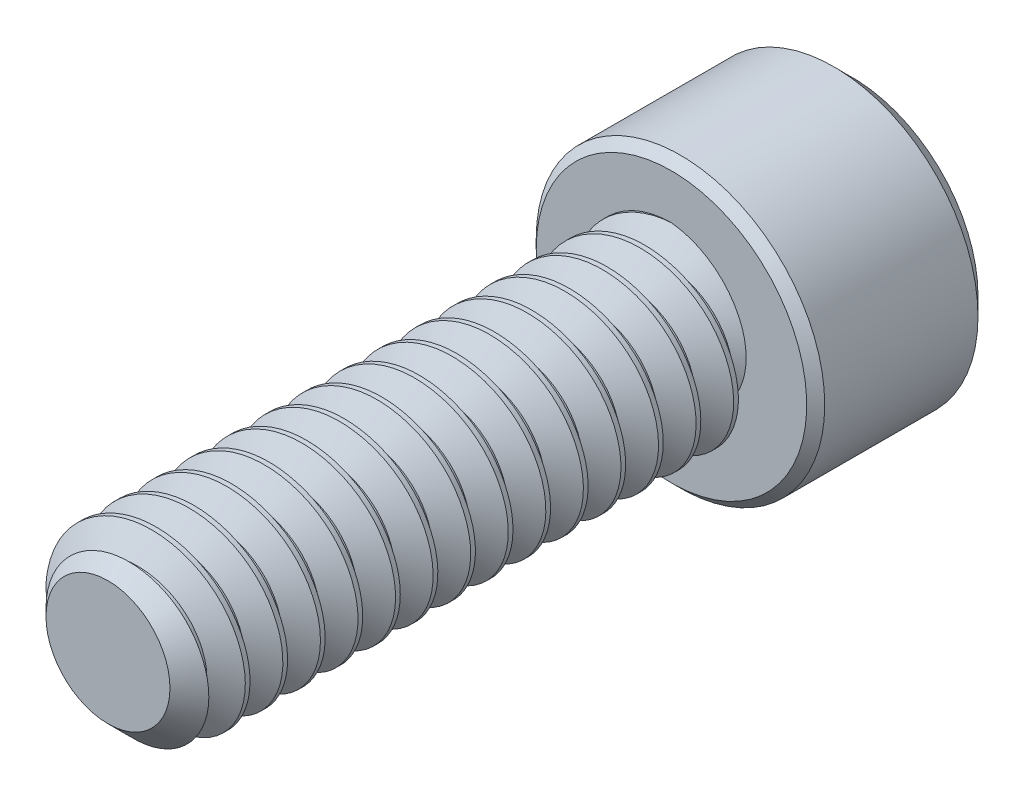
SolidWorks part; units mm, degrees
ref_plane "Front Plane" through (0, 0, 0) normal (0, 0, 1) x (1, 0, 0)
ref_plane "Top Plane" through (0, 0, 0) normal (0, 1, 0) x (1, 0, 0)
ref_plane "Right Plane" through (0, 0, 0) normal (1, 0, 0) x (0, 0, -1)
sketch "Sketch1" plane through (0, 0, 0) normal (0, 0, 1) x (1, 0, 0)
  line L0 (0, 0.762) -> (0, -0.762) construction
  circle A0 centre (0, 0) radius 0.762
  dimension "OD" = 1.524
extrude "Extrude1" add sketch "Sketch1" against normal blind 4.7625
sketch "Sketch2" plane through (0, 0, 0) normal (0, 0, 1) x (1, 0, 0)
  circle A0 centre (0, 0) radius 0.762 construction
  circle A1 centre (0, 0) radius 0.762
curve "Helix/Spiral1" pitch 0.3175 height 5.08 radius 0.762 centre (0, 0, 0) axis (0, 0, -1) start towards (0, 1, 0) parameters "pitch"=0.3175
chamfer "Chamfer3" distance 0.2381 angle 45 1 edges at (0.762, 0, 0)
sketch "Sketch3" plane through (0, 0, 0) normal (1, 0, 0) x (0, 0, -1)
  line L0 (-0.2778, 0.762) -> (-0.1588, 0.5558)
  line L1 (-0.1588, 0.5558) -> (-0.1191, 0.5558)
  line L2 (-0.1191, 0.5558) -> (0, 0.762)
  line L3 (-0.2778, 0.762) -> (0, 0.762)
  line L4 (-0.1389, 0.762) -> (-0.1389, 0.5558) construction
  line L5 (-0.2183, 0.6589) -> (-0.0595, 0.6589) construction
  line L6 (0, 0.762) -> (0, -0.762) construction
  dimension "D1" = 0.0397
  dimension "D2" = 0.1588
  dimension "D3" = 60
sweep "Cut-Sweep1" cut profiles "Sketch3" path "Helix/Spiral1" align with end faces yes
sketch "Sketch6" plane through (0, 0, -4.7625) normal (0, 0, -1) x (-1, 0, 0)
  circle A0 centre (0, 0) radius 1.2192
  dimension "head dia" = 2.4384
extrude "Extrude2" add sketch "Sketch6" along normal blind 1.524
sketch "Sketch7" plane through (0, 0, -6.2865) normal (0, 0, -1) x (-1, 0, 0)
  line L1 (0, 0.7332) -> (-0.635, 0.3666)
  line L2 (-0.635, 0.3666) -> (-0.635, -0.3666)
  line L3 (-0.635, -0.3666) -> (0, -0.7332)
  line L4 (0, -0.7332) -> (0.635, -0.3666)
  line L5 (0.635, -0.3666) -> (0.635, 0.3666)
  line L6 (0.635, 0.3666) -> (0, 0.7332)
  circle A0 centre (0, 0) radius 0.635 construction
  dimension "hex dia" = 1.27
extrude "Cut-Extrude1" cut sketch "Sketch7" against normal blind 0.9525
sketch "Sketch8" plane through (0, 0, -6.2865) normal (0, 0, -1) x (-1, 0, 0)
  circle A0 centre (0, 0) radius 0.7332
extrude "Cut-Extrude2" cut sketch "Sketch8" against normal blind 0.1524 draft 45
chamfer "Chamfer1" distance 0.1524 angle 45 1 edges at (-1.2192, 0, -6.2865)
chamfer "Chamfer2" distance 0.0762 angle 45 1 edges at (-1.2192, 0, -4.7625)
sketch "Sketch9" plane through (0, 0, 0) normal (1, 0, 0) x (0, 0, -1)
  line L0 (0, 0.762) -> (0, -0.762) construction
  line L1 (1.7463, 0.762) -> (1.7463, -0.762) construction
  line L2 (4.7625, 1.2192) -> (4.7625, -1.2192) construction
  line L3 (6.2865, 1.2192) -> (6.2865, -1.2192) construction
  line L4 (6.2865, 0) -> (0, 0) construction
  dimension "D1" = 1.7463
  dimension "D2" = 1.524
  dimension "D3" = 2.4384
  dimension "D4" = 4.7625
equation "\"D3@Helix/Spiral1\" = \"screw length@Extrude1\"+\"pitch@Helix/Spiral1\""
equation "\"D1@Sketch3\" = \"pitch@Helix/Spiral1\"*.125"
equation "\"D2@Sketch3\" = \"pitch@Helix/Spiral1\"*.5"
equation "\"D1@Cut-Extrude1\" = \"hex dia@Sketch7\"*.75"
equation "\"D1@Chamfer1\" = \"head depth@Extrude2\"/10"
equation "\"D1@Sketch9\" = \"pitch@Helix/Spiral1\"*5.5"
equation "\"D1@Chamfer2\" = \"D1@Chamfer1\"/2"
equation "\"D1@Cut-Extrude2\" = \"D1@Chamfer2\"*2"
equation "\"D1@Chamfer3\" = \"pitch@Helix/Spiral1\"*.750"
equation "\"D2@Sketch9\" = \"head depth@Extrude2\""
equation "\"D3@Sketch9\" = \"head dia@Sketch6\""
equation "\"D4@Sketch9\" = \"screw length@Extrude1\""
